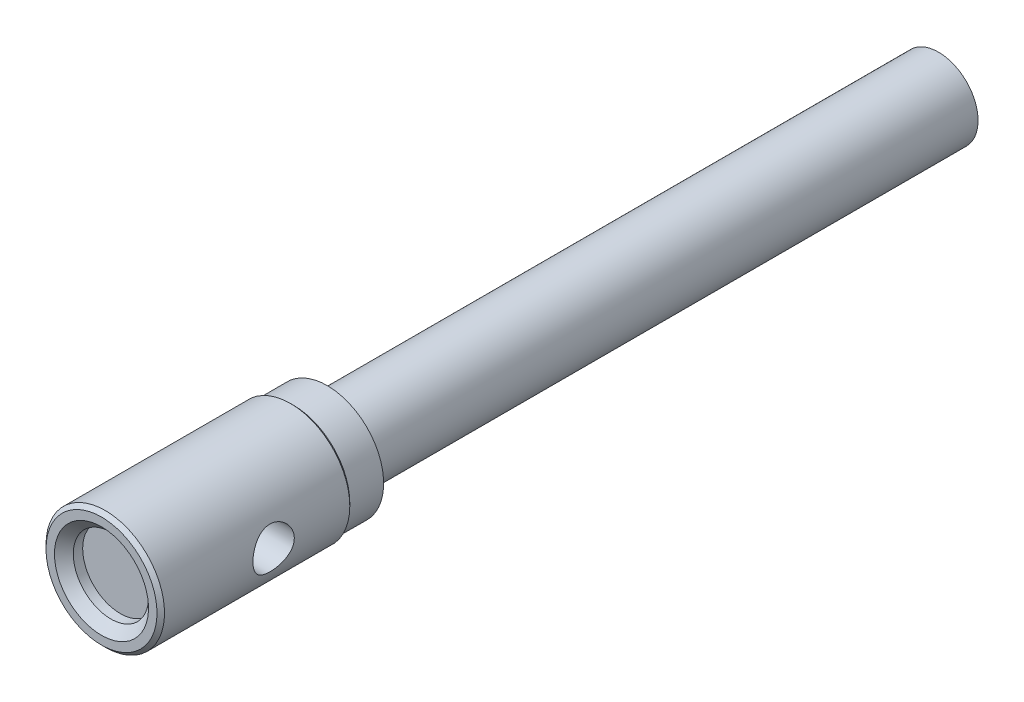
SolidWorks part; units mm, degrees
ref_plane "정면" through (0, 0, 0) normal (0, 0, 1) x (1, 0, 0)
ref_plane "윗면" through (0, 0, 0) normal (0, 1, 0) x (1, 0, 0)
ref_plane "우측면" through (0, 0, 0) normal (1, 0, 0) x (0, 0, -1)
sketch "스케치2" plane through (0, 0, 0) normal (0, 1, 0) x (1, 0, 0)
  line L0 (0, 32.5) -> (0, -11)
  line L1 (0, -11) -> (2, -11)
  line L2 (2, -11) -> (2, -12)
  line L3 (2, -12) -> (3.15, -12)
  line L4 (3.15, -12) -> (3.15, -2)
  line L5 (3.15, -2) -> (3, -2)
  line L6 (3, -2) -> (3, 0)
  line L7 (3, 0) -> (2.1, 0)
  line L8 (2.1, 0) -> (2.1, 32.5)
  line L9 (2.1, 32.5) -> (0, 32.5)
  line L10 (2.1, 0) -> (0, 0) construction
  line L11 (0, 0) -> (0, 32.5) construction
  dimension "D1" = 6
  dimension "D2" = 4.2
  dimension "D3" = 6.3
  dimension "D4" = 10
  dimension "D5" = 2
  dimension "D6" = 1
  dimension "D7" = 32.5
  dimension "D8" = 11
revolve "회전1" add sketch "스케치2" angle 360 about L0
sketch "스케치3" plane through (0, 0, 0) normal (1, 0, 0) x (0, 0, -1)
  line L0 (-6, 0) -> (0, 0) construction
  circle A0 centre (-6, 0) radius 1.1
  dimension "D1" = 2.2
  dimension "D2" = 6
extrude "컷-돌출1" cut sketch "스케치3" against normal through all both and the other way through all
chamfer "모따기1" distance 0.5 angle 45 1 edges at (-2, 0, 12)
chamfer "모따기3" distance 0.2 angle 45 2 edges at (-3.15, 0, 12) (-3, 0, 2)
